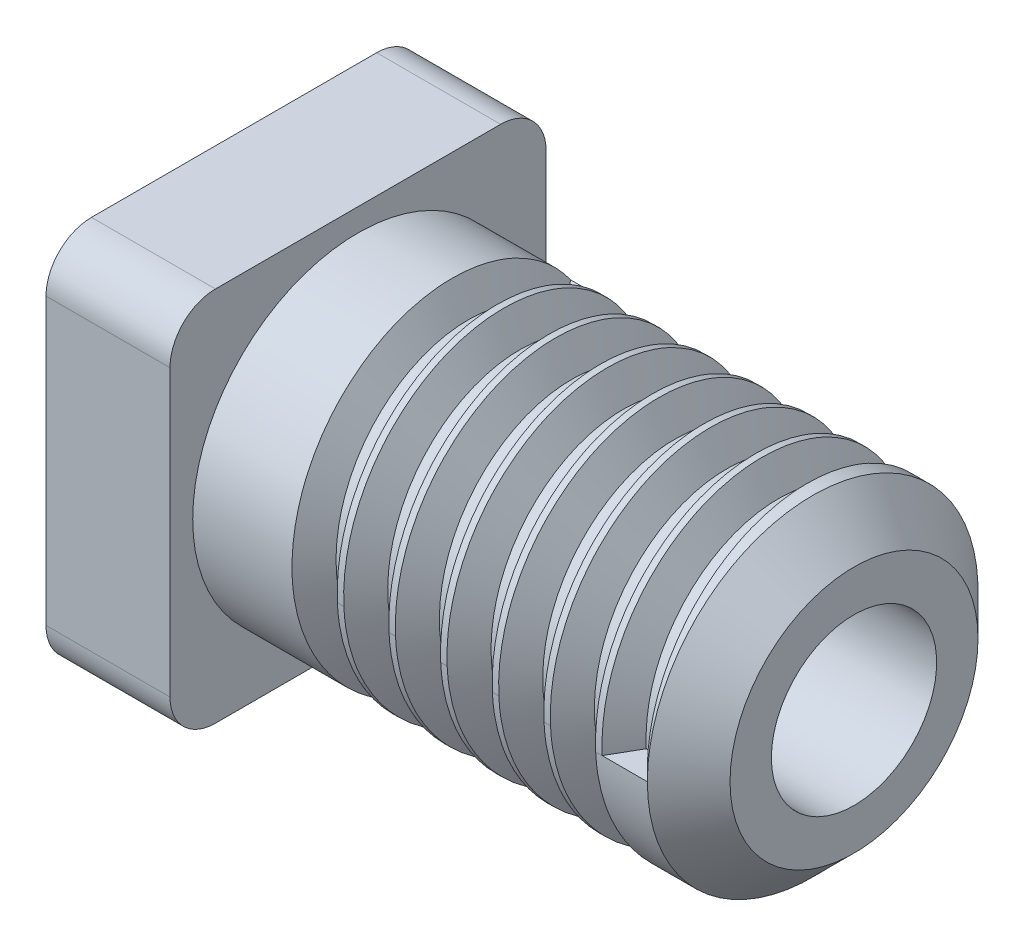
SolidWorks part; units mm, degrees
material "7075-T6 (SN)"
ref_plane "Front Plane" through (0, 0, 0) normal (0, 0, 1) x (1, 0, 0)
ref_plane "Top Plane" through (0, 0, 0) normal (0, 1, 0) x (1, 0, 0)
ref_plane "Right Plane" through (0, 0, 0) normal (1, 0, 0) x (0, 0, -1)
sketch "Sketch1" plane through (0, 0, 0) normal (0, 0, 1) x (1, 0, 0)
  line L0 (-7.5, 10) -> (-4.5, 10)
  line L1 (-4.5, 10) -> (-4.5, 4)
  line L2 (-4.5, 4) -> (7.5, 4)
  line L3 (7.5, 4) -> (7.5, -4)
  line L4 (7.5, -4) -> (-4.5, -4) construction
  line L5 (-4.5, -4) -> (-4.5, -10) construction
  line L6 (-4.5, -10) -> (-7.5, -10) construction
  line L7 (-7.5, -10) -> (-7.5, 10)
  line L8 (55, 0) -> (-55, 0) construction
  line L9 (-7.5, 0) -> (7.5, 0) construction
  line L10 (0, -55) -> (0, 55) construction
  line L11 (-7.5, 2) -> (7.5, 2)
  line L12 (7.5, -2) -> (-7.5, -2) construction
  line L13 (7.5, -2) -> (7.5, -4) construction
  line L14 (7.5, 2) -> (7.5, 4)
  line L15 (-7.5, 10) -> (-7.5, 2)
  line L16 (-7.5, -2) -> (-7.5, -10) construction
  point P2 (-7.5, 0)
  point P11 (7.5, 0)
  point P14 (0, 0)
  dimension "D1" = 20
  dimension "D2" = 4
  dimension "D3" = 8
  dimension "D4" = 3
  dimension "D5" = 15
revolve "Revolve1" add sketch "Sketch1" angle 360 about L9 region at (-6, 9.83, 0)
sketch "Sketch2" plane through (-7.5, 0, 0) normal (-1, 0, 0) x (0, 0, 1)
  line L1 (-4.55, -4.55) -> (4.55, -4.55)
  line L2 (-4.55, -4.55) -> (-4.55, 4.55)
  line L3 (-4.55, 4.55) -> (4.55, 4.55)
  line L4 (4.55, -4.55) -> (4.55, 4.55)
  line L5 (-4.55, -4.55) -> (4.55, 4.55) construction
  line L6 (-4.55, 4.55) -> (4.55, -4.55) construction
  line L7 (-10, -10) -> (10, -10)
  line L8 (-10, -10) -> (-10, 10)
  line L9 (-10, 10) -> (10, 10)
  line L10 (10, -10) -> (10, 10)
  line L11 (-10, -10) -> (10, 10) construction
  line L12 (-10, 10) -> (10, -10) construction
  line L13 (3.7528, 6.5) -> (-3.7528, 6.5) construction
  line L14 (-3.7528, 6.5) -> (-7.5056, 0) construction
  line L15 (-7.5056, 0) -> (-3.7528, -6.5) construction
  line L16 (-3.7528, -6.5) -> (3.7528, -6.5) construction
  line L17 (3.7528, -6.5) -> (7.5056, 0) construction
  line L18 (7.5056, 0) -> (3.7528, 6.5) construction
  circle A0 centre (0, 0) radius 10 construction
  circle A1 centre (0, 0) radius 6.5 construction
  point P0 (0, 0)
  point P6 (0, 0)
  circle M9 centre (0, 0) radius 10
  dimension "D1" = 9.1
  dimension "D2" = 13
extrude "Cut-Extrude1" cut sketch "Sketch2" against normal through all contours L9 L8 M9 | L10 L9 M9 | L8 L7 M9 | L7 L10 M9 | L4 L1 L2 L3 M9 region at (-7.5, -7.7663, -7.7663) region at (-7.5, -7.7663, 7.7663) region at (-7.5, -6.8711, -6.8711) region at (-7.5, 7.7663, -7.7663) region at (-7.5, 7.7663, 7.7663)
chamfer "Chamfer1" distance 1 angle 45 1 edges at (7.5, 0, 4)
cosmetic thread "Cosmetic Thread1" parameters "D1"=8, "D2"=6.619
thread "Thread1" pitch 1.25 method cut trim with start face yes profile "Thread Profile1" start angle 0, offset 0.0001, length 8, pitch 1.25, diameter 8
ref_plane "Plane1" through (6.4999, 0, 4) normal (0, -1, 0) x (0, 0, 1)
sketch "Thread Profile1" plane through (6.4999, 0, 4) normal (0, -1, 0) x (0, 0, 1)
  line L0 (0, 0) -> (0, 1.25) construction
  line L11 (0, 0) -> (0, 1.0937)
  line L12 (0, 1.0937) -> (-0.6766, 0.7031)
  line L13 (-0.6766, 0.7031) -> (-0.6766, 0.3906)
  line L15 (-0.6766, 0.3906) -> (0, 0)
  line L17 (-0.6766, 0.5469) -> (0, 0.5469) construction
  point P2 (0, 0)
  dimension "Pitch" = 1.25
  dimension "Profile_Angle" = 60
  dimension "Profile_Land" = 0.3125
  dimension "Profile_Height" = 0.6766
fillet "Fillet1" radius 1.1 4 edges at (-6, -4.55, 4.55) (-6, -4.55, -4.55) (-6, 4.55, -4.55) (-6, 4.55, 4.55)
